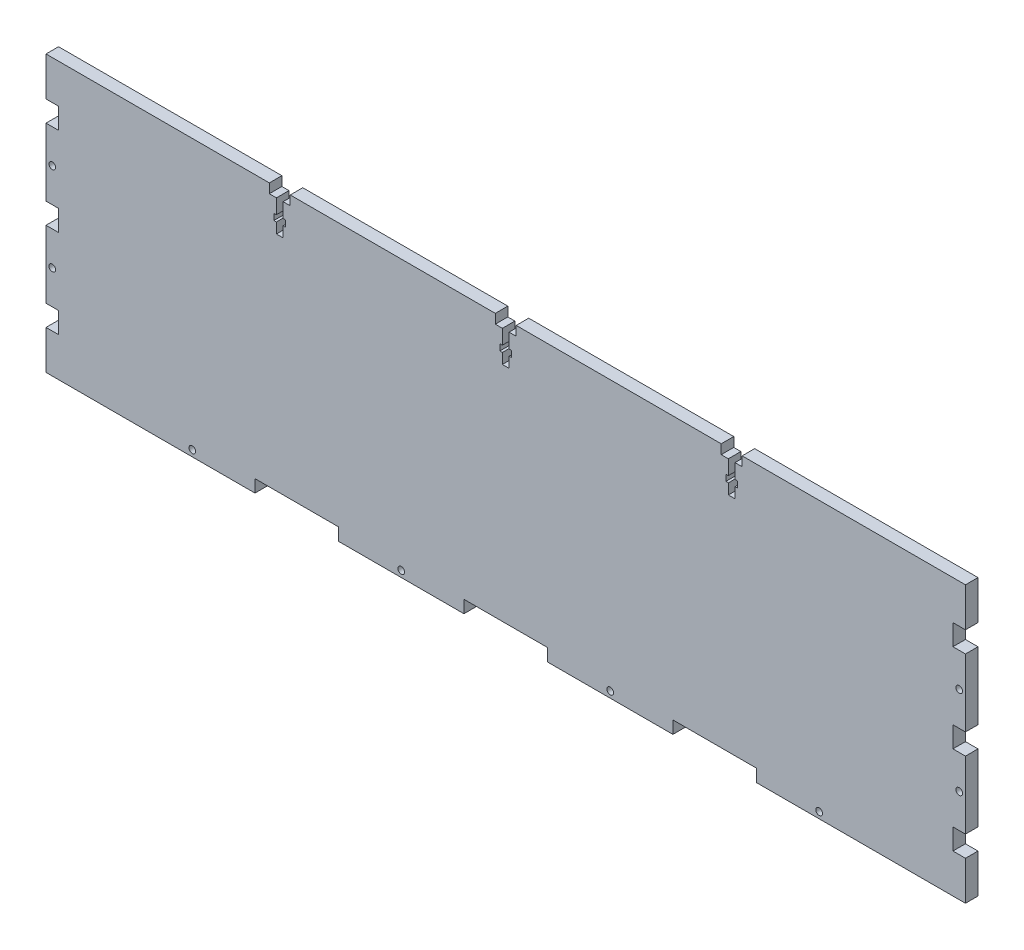
SolidWorks part; units mm, degrees
ref_plane "Front Plane" through (0, 0, 0) normal (0, 0, 1) x (1, 0, 0)
ref_plane "Top Plane" through (0, 0, 0) normal (0, 1, 0) x (1, 0, 0)
ref_plane "Right Plane" through (0, 0, 0) normal (1, 0, 0) x (0, 0, -1)
sketch "Sketch1" plane through (0, 0, 0) normal (0, 0, 1) x (1, 0, 0)
  line L1 (-220, -66) -> (220, -66)
  line L2 (-220, -66) -> (-220, 66)
  line L3 (-220, 66) -> (220, 66)
  line L4 (220, -66) -> (220, 66)
  line L5 (-220, -66) -> (220, 66) construction
  line L6 (-220, 66) -> (220, -66) construction
  point P0 (0, 0)
  dimension "D1" = 440
  dimension "D2" = 132
extrude "Boss-Extrude1" add sketch "Sketch1" along normal blind 6
sketch "Sketch2" plane through (0, 0, 0) normal (0, 0, -1) x (-1, 0, 0)
  line L0 (220, 47.3321) -> (220, 37.3321) construction
  line L1 (220, 37.3321) -> (214, 37.3321) construction
  line L2 (214, 37.3321) -> (214, 47.3321) construction
  line L3 (214, 47.3321) -> (220, 47.3321) construction
  line L12 (220, -37.3321) -> (220, -47.3321) construction
  line L13 (220, -47.3321) -> (214, -47.3321) construction
  line L14 (214, -47.3321) -> (214, -37.3321) construction
  line L15 (214, -37.3321) -> (220, -37.3321) construction
  line L16 (220, 47.3321) -> (220, 37.3321)
  line L17 (220, 37.3321) -> (214, 37.3321)
  line L18 (214, 37.3321) -> (214, 47.3321)
  line L19 (214, 47.3321) -> (220, 47.3321)
  line L20 (220, -37.3321) -> (220, -47.3321)
  line L21 (220, -47.3321) -> (214, -47.3321)
  line L22 (214, -47.3321) -> (214, -37.3321)
  line L23 (214, -37.3321) -> (220, -37.3321)
  line L24 (-214, -37.3321) -> (-214, -47.3321) construction
  line L25 (-214, -47.3321) -> (-220, -47.3321) construction
  line L26 (-220, -47.3321) -> (-220, -37.3321) construction
  line L27 (-220, -37.3321) -> (-214, -37.3321) construction
  line L28 (-214, 47.3321) -> (-214, 37.3321) construction
  line L29 (-214, 37.3321) -> (-220, 37.3321) construction
  line L30 (-220, 37.3321) -> (-220, 47.3321) construction
  line L31 (-220, 47.3321) -> (-214, 47.3321) construction
  line L32 (-214, -37.3321) -> (-214, -47.3321)
  line L33 (-214, -47.3321) -> (-220, -47.3321)
  line L34 (-220, -47.3321) -> (-220, -37.3321)
  line L35 (-220, -37.3321) -> (-214, -37.3321)
  line L36 (-214, 47.3321) -> (-214, 37.3321)
  line L37 (-214, 37.3321) -> (-220, 37.3321)
  line L38 (-220, 37.3321) -> (-220, 47.3321)
  line L39 (-220, 47.3321) -> (-214, 47.3321)
  line L44 (220, -5) -> (220, 5)
  line L45 (214, -5) -> (220, -5)
  line L46 (214, 5) -> (214, -5)
  line L47 (220, 5) -> (214, 5)
  line L48 (220, -5) -> (220, 5)
  line L49 (214, -5) -> (220, -5)
  line L50 (214, 5) -> (214, -5)
  line L51 (220, 5) -> (214, 5)
  line L52 (-214, -5) -> (-214, 5)
  line L53 (-220, -5) -> (-214, -5)
  line L54 (-220, 5) -> (-220, -5)
  line L55 (-214, 5) -> (-220, 5)
  line L56 (-214, -5) -> (-214, 5)
  line L57 (-220, -5) -> (-214, -5)
  line L58 (-220, 5) -> (-220, -5)
  line L59 (-214, 5) -> (-220, 5)
  circle A0 centre (217, 21.1661) radius 1.6 construction
  circle A1 centre (217, -21.1661) radius 1.6 construction
  circle A2 centre (-217, 21.1661) radius 1.6 construction
  circle A3 centre (-217, -21.1661) radius 1.6 construction
  circle A4 centre (217, 21.1661) radius 1.6
  circle A5 centre (217, -21.1661) radius 1.6
  circle A6 centre (-217, 21.1661) radius 1.6
  circle A7 centre (-217, -21.1661) radius 1.6
  dimension "D2" = 0
  dimension "D3" = 0
extrude "Cut-Extrude1" cut sketch "Sketch2" against normal up to next
sketch "Sketch3" plane through (0, 0, 0) normal (0, 0, -1) x (-1, 0, 0)
  circle A0 centre (-150, -63) radius 1.6 construction
  circle A1 centre (-50, -63) radius 1.6 construction
  circle A2 centre (50, -63) radius 1.6 construction
  circle A3 centre (150, -63) radius 1.6 construction
  circle A4 centre (-150, -63) radius 1.6
  circle A5 centre (-50, -63) radius 1.6
  circle A6 centre (50, -63) radius 1.6
  circle A7 centre (150, -63) radius 1.6
extrude "Cut-Extrude2" cut sketch "Sketch3" against normal up to next
sketch "Sketch4" plane through (0, 0, 0) normal (0, 0, -1) x (-1, 0, 0)
  line L0 (80, -66) -> (120, -66) construction
  line L1 (120, -66) -> (120, -60) construction
  line L2 (120, -60) -> (80, -60) construction
  line L3 (80, -60) -> (80, -66) construction
  line L4 (-20, -66) -> (20, -66) construction
  line L5 (20, -66) -> (20, -60) construction
  line L6 (20, -60) -> (-20, -60) construction
  line L7 (-20, -60) -> (-20, -66) construction
  line L8 (-120, -66) -> (-80, -66) construction
  line L9 (-80, -66) -> (-80, -60) construction
  line L10 (-80, -60) -> (-120, -60) construction
  line L11 (-120, -60) -> (-120, -66) construction
  line L12 (80, -66) -> (120, -66)
  line L13 (120, -66) -> (120, -60)
  line L14 (120, -60) -> (80, -60)
  line L15 (80, -60) -> (80, -66)
  line L16 (-20, -66) -> (20, -66)
  line L17 (20, -66) -> (20, -60)
  line L18 (20, -60) -> (-20, -60)
  line L19 (-20, -60) -> (-20, -66)
  line L20 (-120, -66) -> (-80, -66)
  line L21 (-80, -66) -> (-80, -60)
  line L22 (-80, -60) -> (-120, -60)
  line L23 (-120, -60) -> (-120, -66)
extrude "Cut-Extrude3" cut sketch "Sketch4" against normal up to next
sketch "Sketch5" plane through (0, 66, 0) normal (0, 1, 0) x (1, 0, 0)
  line L0 (220, 0) -> (-220, 0) construction
  line L1 (-113.125, -6) -> (-103.125, -6)
  line L2 (-113.125, -6) -> (-113.125, 0)
  line L3 (-113.125, 0) -> (-103.125, 0)
  line L4 (-103.125, -6) -> (-103.125, 0)
  line L5 (-113.125, -6) -> (-103.125, 0) construction
  line L6 (-113.125, 0) -> (-103.125, -6) construction
  line L7 (-103.125, -6) -> (-103.125, 0) construction
  line L8 (5, -6) -> (5, 0) construction
  line L9 (-5, -6) -> (5, -6)
  line L10 (-5, -6) -> (-5, 0)
  line L11 (-5, 0) -> (5, 0)
  line L12 (5, -6) -> (5, 0)
  line L13 (-5, -6) -> (5, 0) construction
  line L14 (-5, 0) -> (5, -6) construction
  line L15 (113.125, -6) -> (113.125, 0) construction
  line L16 (103.125, -6) -> (113.125, -6)
  line L17 (103.125, -6) -> (103.125, 0)
  line L18 (103.125, 0) -> (113.125, 0)
  line L19 (113.125, -6) -> (113.125, 0)
  line L20 (103.125, -6) -> (113.125, 0) construction
  line L21 (103.125, 0) -> (113.125, -6) construction
  point P0 (-108.125, -3)
  point P10 (0, -3)
  point P18 (108.125, -3)
extrude "Cut-Extrude4" cut sketch "Sketch5" against normal blind 4.5
sketch "Sketch6" plane through (0, 0, 0) normal (0, 0, -1) x (-1, 0, 0)
  line L0 (-108.125, 61.5) -> (-108.125, 46.5) construction
  line L1 (-113.125, 61.5) -> (-103.125, 61.5) construction
  line L2 (-109.725, 61.5) -> (-109.725, 54.5)
  line L3 (-106.525, 61.5) -> (-106.525, 54.5)
  line L4 (-109.725, 61.5) -> (-106.525, 61.5)
  line L5 (-109.725, 46.5) -> (-106.525, 46.5)
  line L6 (-106.525, 51.5) -> (-105.325, 51.5)
  line L7 (-110.925, 54.5) -> (-109.725, 54.5)
  line L8 (-110.925, 54.5) -> (-110.925, 51.5)
  line L9 (-110.925, 51.5) -> (-109.725, 51.5)
  line L10 (-105.325, 54.5) -> (-105.325, 51.5)
  line L11 (-110.925, 54.5) -> (-105.325, 51.5) construction
  line L12 (-110.925, 51.5) -> (-105.325, 54.5) construction
  line L13 (-106.525, 51.5) -> (-106.525, 46.5)
  line L14 (-106.525, 61.5) -> (-106.525, 46.5) construction
  line L15 (-109.725, 51.5) -> (-109.725, 46.5)
  line L16 (-109.725, 61.5) -> (-109.725, 46.5) construction
  line L17 (-106.525, 54.5) -> (-105.325, 54.5)
  line L18 (-1.595, 61.5) -> (-1.595, 54.5)
  line L19 (1.605, 61.5) -> (1.605, 54.5)
  line L20 (-1.595, 61.5) -> (1.605, 61.5)
  line L21 (-1.595, 46.5) -> (1.605, 46.5)
  line L22 (1.605, 51.5) -> (2.805, 51.5)
  line L23 (-2.795, 54.5) -> (-1.595, 54.5)
  line L24 (-2.795, 54.5) -> (-2.795, 51.5)
  line L25 (-2.795, 51.5) -> (-1.595, 51.5)
  line L26 (2.805, 54.5) -> (2.805, 51.5)
  line L27 (1.605, 51.5) -> (1.605, 46.5)
  line L28 (-1.595, 51.5) -> (-1.595, 46.5)
  line L29 (1.605, 54.5) -> (2.805, 54.5)
  line L30 (0.005, 61.5) -> (0.005, 46.5) construction
  line L31 (-2.795, 54.5) -> (2.805, 51.5) construction
  line L32 (-2.795, 51.5) -> (2.805, 54.5) construction
  line L33 (106.535, 61.5) -> (106.535, 54.5)
  line L34 (109.735, 61.5) -> (109.735, 54.5)
  line L35 (106.535, 61.5) -> (109.735, 61.5)
  line L36 (106.535, 46.5) -> (109.735, 46.5)
  line L37 (109.735, 51.5) -> (110.935, 51.5)
  line L38 (105.335, 54.5) -> (106.535, 54.5)
  line L39 (105.335, 54.5) -> (105.335, 51.5)
  line L40 (105.335, 51.5) -> (106.535, 51.5)
  line L41 (110.935, 54.5) -> (110.935, 51.5)
  line L42 (109.735, 51.5) -> (109.735, 46.5)
  line L43 (106.535, 51.5) -> (106.535, 46.5)
  line L44 (109.735, 54.5) -> (110.935, 54.5)
  line L45 (108.135, 61.5) -> (108.135, 46.5) construction
  line L46 (105.335, 54.5) -> (110.935, 51.5) construction
  line L47 (105.335, 51.5) -> (110.935, 54.5) construction
  point P8 (-108.125, 53)
  point P25 (0.005, 53)
  point P40 (108.135, 53)
  dimension "D1" = 15
  dimension "D4" = 5.6
  dimension "D5" = 3
  dimension "D6" = 7
  dimension "D2" = 1.6
  dimension "D3" = 1.6
  dimension "D7" = 3
extrude "Cut-Extrude5" cut sketch "Sketch6" against normal up to next
equation "\"m3_depth\"=15"
equation "\"D1@Sketch6\"=\"m3_depth\""
equation "\"m3_nut_width\"=5.6"
equation "\"D4@Sketch6\"=\"m3_nut_width\""
equation "\"m3_nut_thickness\"=3"
equation "\"D5@Sketch6\"=\"m3_nut_thickness\""
equation "\"m3_nut_depth\"=7"
equation "\"D6@Sketch6\"=\"m3_nut_depth\""
